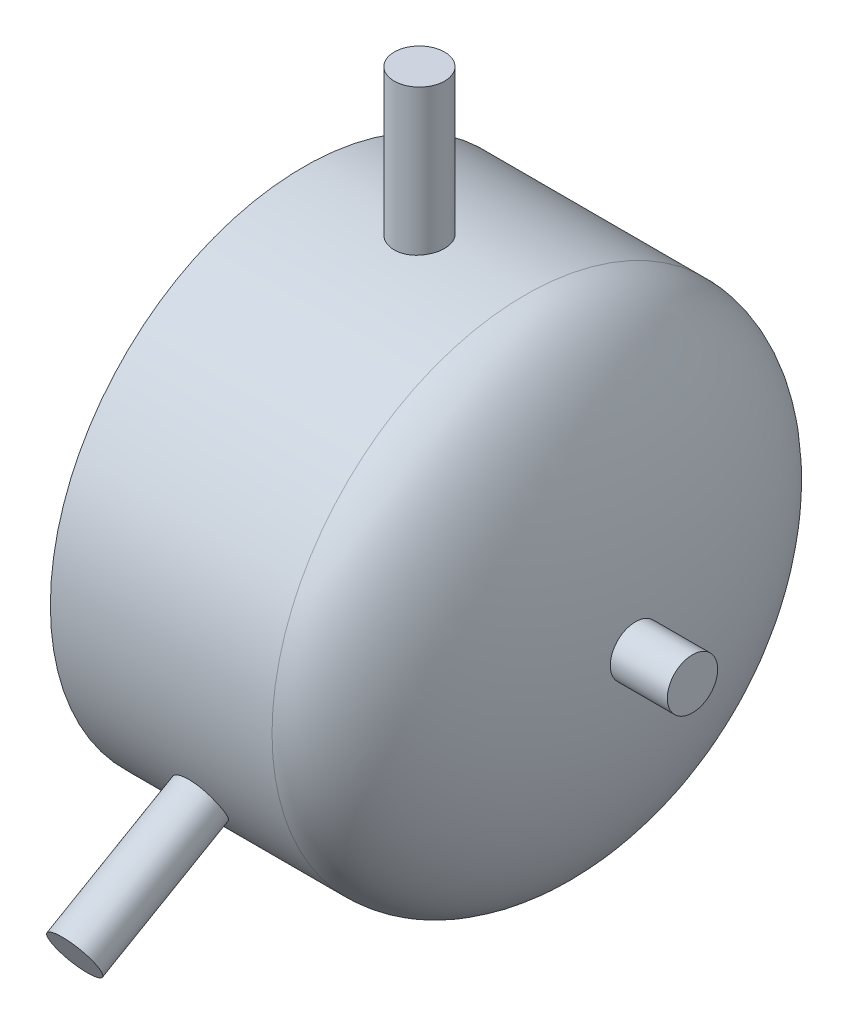
SolidWorks part; units mm, degrees
ref_plane "Front Plane" through (0, 0, 0) normal (0, 0, 1) x (1, 0, 0)
ref_plane "Top Plane" through (0, 0, 0) normal (0, 1, 0) x (1, 0, 0)
ref_plane "Right Plane" through (0, 0, 0) normal (1, 0, 0) x (0, 0, -1)
sketch "Sketch0" plane through (0, 0, 0) normal (0, 0, 1) x (1, 0, 0)
  line L3 (-41.91, 0) -> (41.91, 0) construction
  line L4 (-41.91, 63.8175) -> (-41.91, -63.8175) construction
  line L5 (13.97, 57.0357) -> (-41.91, 57.3786) construction
  line L6 (13.97, 57.0357) -> (13.97, -57.0357) construction
  line L7 (13.97, -57.0357) -> (-41.91, -57.3786) construction
  line L8 (-41.91, 57.3786) -> (-41.91, -57.3786) construction
  line L14 (13.97, 51.1302) -> (13.97, -51.1302) construction
  point P0 (13.97, 0)
  dimension "H" = 27.94
  dimension "M" = 127.635
  dimension "OD A" = 114.7572
  dimension "OD B" = 114.0714
  dimension "ID" = 102.2604
  dimension "L" = 83.82
  dimension "C" = 55.88
sketch "Sketch1" plane through (0, 0, 0) normal (0, 0, 1) x (1, 0, 0)
  line L1 (-41.91, 0) -> (41.91, 0) construction
  line L2 (-41.91, 0) -> (41.91, 0) construction
  line L3 (35.1282, 0) -> (41.91, 0)
  line L4 (-41.91, -63.8175) -> (-41.91, -57.3786)
  line L5 (-41.91, -57.3786) -> (13.97, -57.0357)
  line L6 (13.97, -57.0357) -> (13.97, -63.8175) construction
  line L9 (13.97, -63.8175) -> (-41.91, -63.8175)
  ellipse E2 centre (13.97, 0) end of major axis (13.97, 63.8175) minor radius 27.94 (13.97, -63.8175) -> (41.91, 0) ccw
  ellipse E3 centre (13.97, 0) end of major axis (13.97, -57.0357) minor radius 21.1582 (13.97, -57.0357) -> (35.1282, 0) ccw
revolve "Revolve1" add sketch "Sketch1" angle 360 about L1
sketch "Sketch2" plane through (0, 0, 0) normal (0, 0, 1) x (1, 0, 0)
  line L0 (-12.7, -906.9498) -> (-12.7, 49093.0502) construction
  line L2 (0, -70.1993) -> (0, 70.1993) construction
  line L3 (-1105.2401, 0) -> (48894.7599, 0) construction
  line L4 (-19.05, 100.33) -> (-12.7, 100.33)
  line L5 (-19.05, 100.33) -> (-19.05, 57.912)
  line L6 (-19.05, 57.912) -> (-12.7, 57.912)
  line L7 (-12.7, 100.33) -> (-12.7, 57.912)
  dimension "D1" = 12.7
  dimension "D2" = 200.66
  dimension "D3" = 57.912
  dimension "D4" = 12.7
revolve "Revolve2" add sketch "Sketch2" angle 360 about L0
ref_axis "Axis1" through (-46.101, 0, 0) along (1, 0, 0)
pattern_circular "CirPattern1" count 3 over 360 about axis through (-46.101, 0, 0) along (1, 0, 0) of bodies 105
sketch "Sketch3" plane through (0, 0, 0) normal (0, 0, 1) x (1, 0, 0)
  line L0 (-1078.0639, 0) -> (48921.9361, 0) construction
  line L1 (13.97, 63.8175) -> (13.97, -63.8175) construction
  line L2 (38.1, 0) -> (56.134, 0)
  line L3 (38.1, 0) -> (38.1, 6.35)
  line L4 (38.1, 6.35) -> (56.134, 6.35)
  line L5 (56.134, 0) -> (56.134, 6.35)
  dimension "D1" = 42.164
  dimension "D2" = 12.7
  dimension "D3" = 24.13
revolve "Revolve3" add sketch "Sketch3" angle 360 about L0
